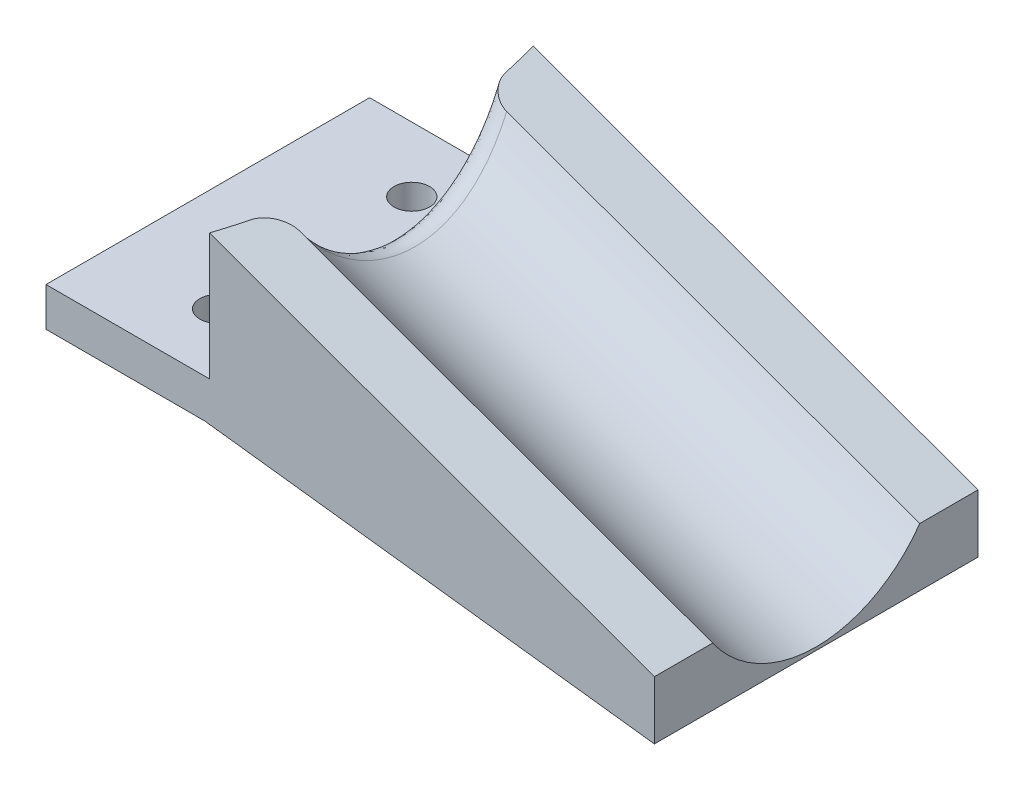
SolidWorks part; units mm, degrees
ref_plane "前视基准面" through (0, 0, 0) normal (0, 0, 1) x (1, 0, 0)
ref_plane "上视基准面" through (0, 0, 0) normal (0, 1, 0) x (1, 0, 0)
ref_plane "右视基准面" through (0, 0, 0) normal (1, 0, 0) x (0, 0, -1)
sketch "草图1" plane through (0, 0, 0) normal (0, 0, 1) x (1, 0, 0)
  line L0 (-24.5153, 0) -> (0, 0)
  line L1 (0, 0) -> (69.4847, -8.4779)
  line L2 (69.4847, -8.4779) -> (69.4847, 0.5221)
  line L3 (69.4847, 0.5221) -> (-0.5153, 26)
  line L4 (-0.5153, 26) -> (-24.5153, 26)
  line L5 (-24.5153, 26) -> (-24.5153, 0)
  point P2 (68.8102, -12.8513)
  point P8 (67.5428, 2.8063)
  point P9 (69.1164, -11.0871)
  point P10 (0, 0)
  point P11 (0, 0)
  point P12 (0, 0)
  point P13 (68.795, -12.9324)
  dimension "D1" = 26
  dimension "D2" = 24
  dimension "D3" = 70
  dimension "D4" = 70
  dimension "D5" = 160
  dimension "D6" = 9
extrude "凸台-拉伸1" add sketch "草图1" along normal blind 50
ref_axis "基准轴1" through (69.4847, 0.5221, 50) along (-0.9397, 0.342, 0)
ref_plane "基准面2" through (-8.8113, 3.207, 0) normal (-0.9397, 0.342, 0) x (0, 0, 1)
sketch "草图4" plane through (-8.8113, 3.207, 0) normal (-0.9397, 0.342, 0) x (0, 0, 1)
  line L0 (25, 24.2558) -> (25, 45.4001) construction
  line L1 (50, 24.2558) -> (0, 24.2558) construction
  circle A0 centre (25, 36.2558) radius 20
  point P6 (41, 24.2558)
  dimension "D1" = 40
  dimension "D2" = 9
extrude "切除-拉伸1" cut sketch "草图4" against normal through all contours A0
sketch "草图6" plane through (0, 26, 0) normal (0, 1, 0) x (1, 0, 0)
  line L0 (-139.6386, -25) -> (46.7906, -25) construction
  line L1 (-24.5153, -50) -> (-24.5153, 0) construction
  circle A0 centre (-112.0153, -25) radius 115.5
  point P4 (3.4847, -25)
  dimension "D1" = 231
  dimension "D2" = 28
extrude "切除-拉伸3" cut sketch "草图6" against normal blind 20
sketch "草图8" plane through (0, 0, 0) normal (0, -1, 0) x (1, 0, 0)
  line L0 (69.4847, 25) -> (-34.9202, 25) construction
  line L1 (69.4847, 50) -> (69.4847, 0) construction
  line L3 (0, 50) -> (0, 0) construction
  circle A0 centre (-8, 40) radius 2.75
  circle A1 centre (-8, 10) radius 2.75
  dimension "D1" = 5.5
  dimension "D2" = 15
  dimension "D3" = 8
extrude "切除-拉伸4" cut sketch "草图8" against normal blind 10
fillet "圆角1" radius 3 1 edges at (3.474, 16.1007, 26.5749)
